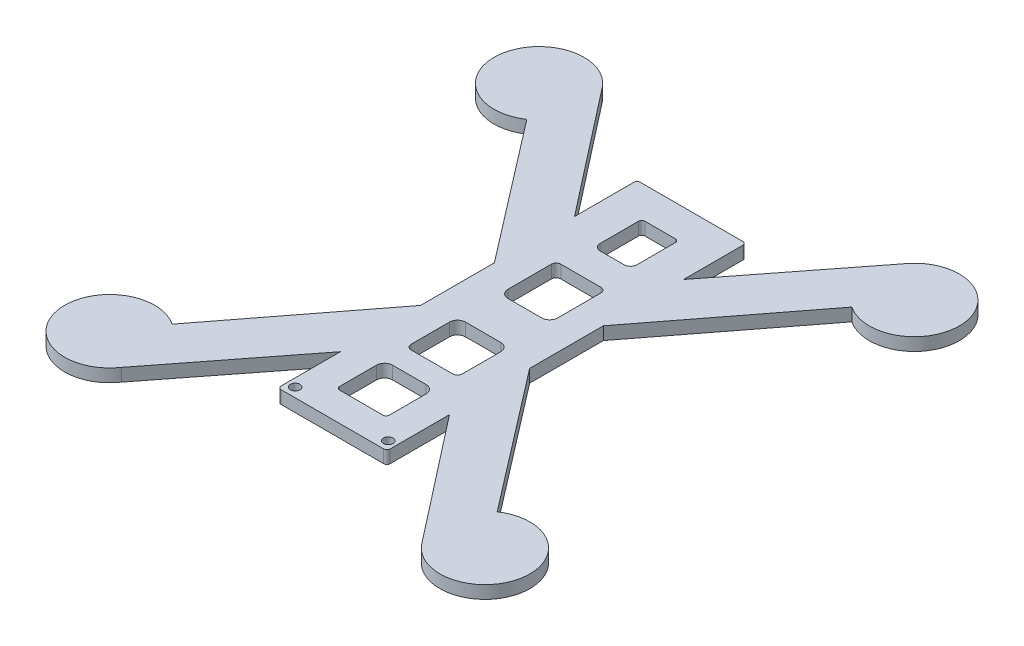
SolidWorks part; units mm, degrees
ref_plane "Front Plane" through (0, 0, 0) normal (0, 0, 1) x (1, 0, 0)
ref_plane "Top Plane" through (0, 0, 0) normal (0, 1, 0) x (1, 0, 0)
ref_plane "Right Plane" through (0, 0, 0) normal (1, 0, 0) x (0, 0, -1)
sketch "Frame Sketch" plane through (0, 0, 0) normal (0, 1, 0) x (1, 0, 0)
  line L0 (2, 0) -> (2, 126.6085) construction
  line L5 (-15, 11.5) -> (-48.6747, 55.2899)
  line L6 (-48.6747, 0) -> (67.0859, 0) construction
  line L11 (2, 0) -> (2, -105.8001) construction
  line L22 (-15, 36.5) -> (-46.0248, 76.2899)
  line L23 (-15, 56) -> (18, 56)
  line L24 (-15, 56) -> (-15, -55)
  line L25 (-14, -56) -> (19, -56)
  line L26 (19, 55) -> (19, -56)
  line L27 (-15, 56) -> (19, -56) construction
  line L28 (-15, -56) -> (19, 56) construction
  line L29 (-15, -11.5) -> (-48.6747, -55.2899)
  line L30 (-15, -36.5) -> (-15, -11.5)
  line L31 (-15, -36.5) -> (-46.0248, -76.2899)
  line L32 (-48.6747, -55.2899) -> (-46.0248, -76.2899)
  line L33 (19, -36.5) -> (19, -11.5)
  line L34 (19, -36.5) -> (50.0248, -76.2899)
  line L35 (-15, 36.5) -> (-15, 11.5)
  line L36 (-48.6747, 55.2899) -> (-46.0248, 76.2899)
  line L37 (52.6747, -55.2899) -> (50.0248, -76.2899)
  line L38 (19, -11.5) -> (52.6747, -55.2899)
  line L39 (19, 11.5) -> (52.6747, 55.2899)
  line L40 (19, 36.5) -> (19, 11.5)
  line L41 (19, 36.5) -> (50.0248, 76.2899)
  line L42 (52.6747, 55.2899) -> (50.0248, 76.2899)
  line L44 (-4.75, -47) -> (8.75, -47)
  line L45 (-5.75, -46) -> (-5.75, -34.5)
  line L46 (-3.25, -32) -> (7.25, -32)
  line L47 (9.75, -46) -> (9.75, -34.5)
  line L48 (-5.75, -47) -> (9.75, -32) construction
  line L49 (-5.75, -32) -> (9.75, -47) construction
  line L50 (8.5, -25) -> (-4.5, -25)
  line L51 (10, -23.5) -> (10, -11.5)
  line L52 (7.5, -9) -> (-3.5, -9)
  line L53 (-6, -23.5) -> (-6, -11.5)
  line L54 (10, -25) -> (-6, -9) construction
  line L55 (10, -9) -> (-6, -25) construction
  line L56 (-3.25, 4) -> (7.25, 4)
  line L57 (-5.75, 6.5) -> (-5.75, 20)
  line L58 (-4.25, 21.5) -> (8.25, 21.5)
  line L59 (9.75, 6.5) -> (9.75, 20)
  line L60 (-5.75, 4) -> (9.75, 21.5) construction
  line L61 (-5.75, 21.5) -> (9.75, 4) construction
  line L62 (-1.75, 31.1991) -> (5.75, 31.1991)
  line L63 (-3.75, 33.1991) -> (-3.75, 45.1991)
  line L64 (-2.75, 46.1991) -> (6.75, 46.1991)
  line L65 (7.75, 33.1991) -> (7.75, 45.1991)
  line L66 (-3.75, 31.1991) -> (7.75, 46.1991) construction
  line L67 (-3.75, 46.1991) -> (7.75, 31.1991) construction
  circle A0 centre (-56.5031, 66.9449) radius 14.04
  circle A5 centre (-56.5031, -66.9449) radius 14.04
  circle A6 centre (60.5031, -66.9449) radius 14.04
  circle A7 centre (60.5031, 66.9449) radius 14.04
  arc A8 (19, 55) -> (18, 56) centre (18, 55) ccw
  arc A9 (19, -55) -> (18, -56) centre (18, -55) cw
  arc A10 (-15, 55) -> (-14, 56) centre (-14, 55) cw
  arc A11 (-14, -56) -> (-15, -55) centre (-14, -55) cw
  circle A12 centre (-12.5, -53.1) radius 1.5
  circle A13 centre (16.5, -53.1) radius 1.5
  arc A14 (9.75, -46) -> (8.75, -47) centre (8.75, -46) cw
  arc A15 (-4.75, -47) -> (-5.75, -46) centre (-4.75, -46) cw
  arc A16 (-5.75, -34.5) -> (-3.25, -32) centre (-3.25, -34.5) cw
  arc A17 (7.25, -32) -> (9.75, -34.5) centre (7.25, -34.5) cw
  arc A18 (10, -23.5) -> (8.5, -25) centre (8.5, -23.5) cw
  arc A19 (-6, -23.5) -> (-4.5, -25) centre (-4.5, -23.5) ccw
  arc A20 (10, -11.5) -> (7.5, -9) centre (7.5, -11.5) ccw
  arc A21 (-3.5, -9) -> (-6, -11.5) centre (-3.5, -11.5) ccw
  arc A22 (-3.25, 4) -> (-5.75, 6.5) centre (-3.25, 6.5) cw
  arc A23 (9.75, 6.5) -> (7.25, 4) centre (7.25, 6.5) cw
  arc A24 (-4.25, 21.5) -> (-5.75, 20) centre (-4.25, 20) ccw
  arc A25 (9.75, 20) -> (8.25, 21.5) centre (8.25, 20) ccw
  arc A26 (-1.75, 31.1991) -> (-3.75, 33.1991) centre (-1.75, 33.1991) cw
  arc A27 (7.75, 33.1991) -> (5.75, 31.1991) centre (5.75, 33.1991) cw
  arc A28 (-2.75, 46.1991) -> (-3.75, 45.1991) centre (-2.75, 45.1991) ccw
  arc A29 (7.75, 45.1991) -> (6.75, 46.1991) centre (6.75, 45.1991) ccw
  point P0 (0, 0)
  point P6 (0, 0)
  point P52 (2, -39.5)
  point P69 (2, -17)
  point P86 (2, 12.75)
  point P103 (2, 38.6991)
  dimension "D6" = 1
  dimension "D7" = 2.9
  dimension "D8" = 2.5
  dimension "D5" = 16
  dimension "D11" = 9
  dimension "D12" = 9.25
  dimension "D13" = 2.5
  dimension "D14" = 2.5
  dimension "D17" = 1.5
  dimension "D18" = 1.5
  dimension "D19" = 2.5
  dimension "D20" = 2.5
  dimension "D23" = 2.5
  dimension "D24" = 2.5
  dimension "D25" = 1.5
  dimension "D26" = 1.5
  dimension "D1" = 25
  dimension "D2" = 21
  dimension "D3" = 112
  dimension "D4" = 34
  dimension "D9" = 15
  dimension "D10" = 15.5
  dimension "D15" = 16
  dimension "D16" = 7
  dimension "D21" = 17.5
  dimension "D22" = 15.5
  dimension "D27" = 13
  dimension "D28" = 15
  dimension "D29" = 11.5
extrude "Frame Bottom Plate" add sketch "Frame Sketch" along normal blind 4 contours L26 L23 L24 L25 | L37 A6 | L34 L37 L38 L33 | L39 L42 L41 L40 | A7 | L22 L36 L5 L35 | A0 | L29 L32 L31 L30 | A5 region at (2, 0, -1.4277) region at (61.9322, 0, 67.1253)
